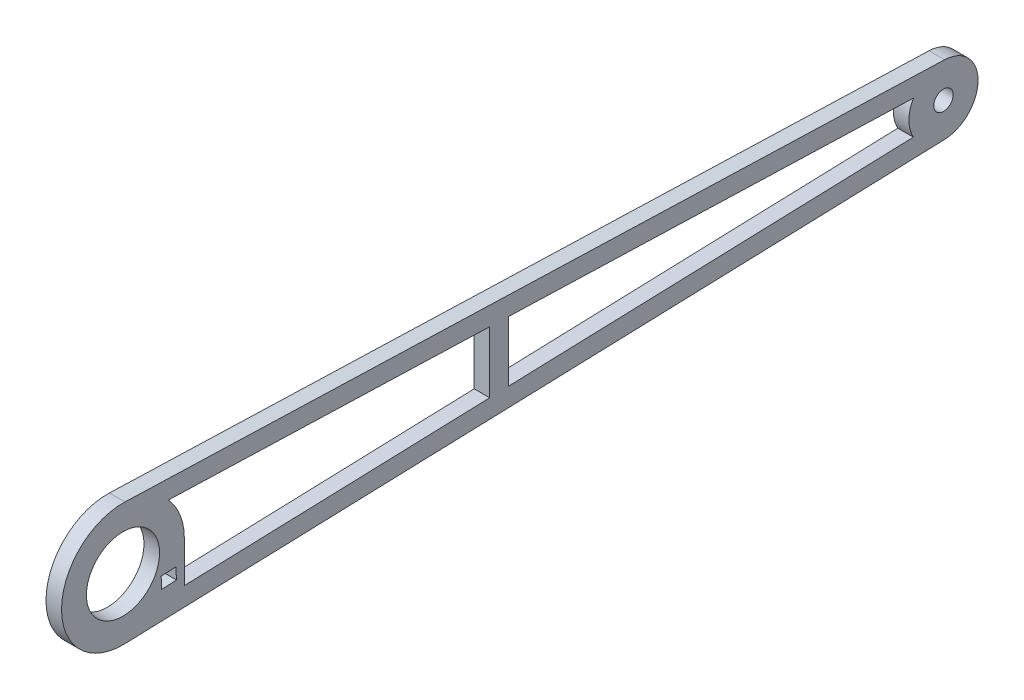
SolidWorks part; units mm, degrees
material "Delrin"
ref_plane "Front Plane" through (0, 0, 0) normal (0, 0, 1) x (1, 0, 0)
ref_plane "Top Plane" through (0, 0, 0) normal (0, 1, 0) x (1, 0, 0)
ref_plane "Right Plane" through (0, 0, 0) normal (1, 0, 0) x (0, 0, -1)
sketch "Sketch1" plane through (0, 0, 0) normal (1, 0, 0) x (0, 0, -1)
  line L0 (0.2053, 6.2704) -> (83.9355, 3.5287)
  line L1 (0, -6.2772) -> (83.9355, -3.5287)
  line L2 (-1000, 0) -> (49000, 0) construction
  line L3 (4.6432, 4.2191) -> (80.7408, 1.7273)
  line L4 (4.6432, -4.2191) -> (80.7408, -1.7273)
  line L5 (0.143, 4.3665) -> (83.8732, 1.6247) construction
  line L6 (-0.0623, -4.3732) -> (83.8732, -1.6247) construction
  line L7 (83.82, -1000) -> (83.82, 49000) construction
  line L8 (5.5059, -3.3041) -> (5.447, -2.0355) construction
  line L9 (5.447, -2.0355) -> (3.8612, -2.1091) construction
  line L10 (3.9201, -3.3777) -> (3.8612, -2.1091) construction
  line L11 (5.5059, -3.3041) -> (3.9201, -3.3777) construction
  line L12 (5.5059, -3.3041) -> (5.447, -2.0355) construction
  line L13 (5.447, -2.0355) -> (3.8612, -2.1091) construction
  line L14 (3.9201, -3.3777) -> (3.8612, -2.1091) construction
  line L15 (5.5059, -3.3041) -> (3.9201, -3.3777) construction
  line L16 (6.2738, 0) -> (6.2738, -4.1657)
  line L17 (39.37, 3.082) -> (39.37, -3.082)
  line L18 (37.465, 3.1444) -> (37.465, -3.1444)
  line L19 (5.4107, -2.0753) -> (3.901, -2.1454)
  line L20 (3.9564, -3.3379) -> (3.901, -2.1454)
  line L21 (5.4661, -3.2678) -> (3.9564, -3.3379)
  line L22 (5.4661, -3.2678) -> (5.4107, -2.0753)
  circle A0 centre (0, 0) radius 3.7338
  circle A1 centre (0, 0) radius 6.2738
  circle A2 centre (83.82, 0) radius 0.9906
  circle A3 centre (83.82, 0) radius 3.5306
  circle A4 centre (83.82, 15.875) radius 1.016
  circle A5 centre (83.82, 15.875) radius 3.556
  dimension "D1" = 7.4676
  dimension "D2" = 2.54
  dimension "D3" = 1.9812
  dimension "D8" = 2.032
  dimension "D5" = 83.82
  dimension "D10" = 15.875
  dimension "D11" = 44.45
  dimension "D12" = 1.905
  dimension "D4" = 2.54
  dimension "D6" = 1.905
  dimension "D7" = 1.905
  dimension "D9" = 2.54
  dimension "D13" = 0.0381
extrude "Boss-Extrude1" add sketch "Sketch1" along normal blind 1.5875 contours A1 L2 A0 | A1 L2 A3 L0 | L2 A1 L1 A3 | A3 L2 A2 | A1 L4 L16 | L3 L18 L4 L17 region at (0, 3.9454, -42.4708) region at (0, 5.5338, -2.5579) region at (0, 2.3859, -86.2853) region at (0, -3.9454, -42.4708) region at (0, 0, -38.4143) region at (0, -3.1728, -5.801)
sketch3d "3DSketch1"
  line L0 (0, 6.2704, -0.2053) -> (0, 3.5287, -83.9355) construction
  line L1 (0, 3.5649, -82.8294) -> (1.5875, 3.5649, -82.8294)
  line L2 (0, 3.5649, -82.8294) -> (0, -3.5649, -82.8294)
  line L3 (0, -3.5649, -82.8294) -> (1.5875, -3.5649, -82.8294)
  line L4 (1.5875, 3.5649, -82.8294) -> (1.5875, -3.5649, -82.8294)
  line L5 (1.5875, -6.2704, -0.2053) -> (1.5875, -3.5287, -83.9355) construction
